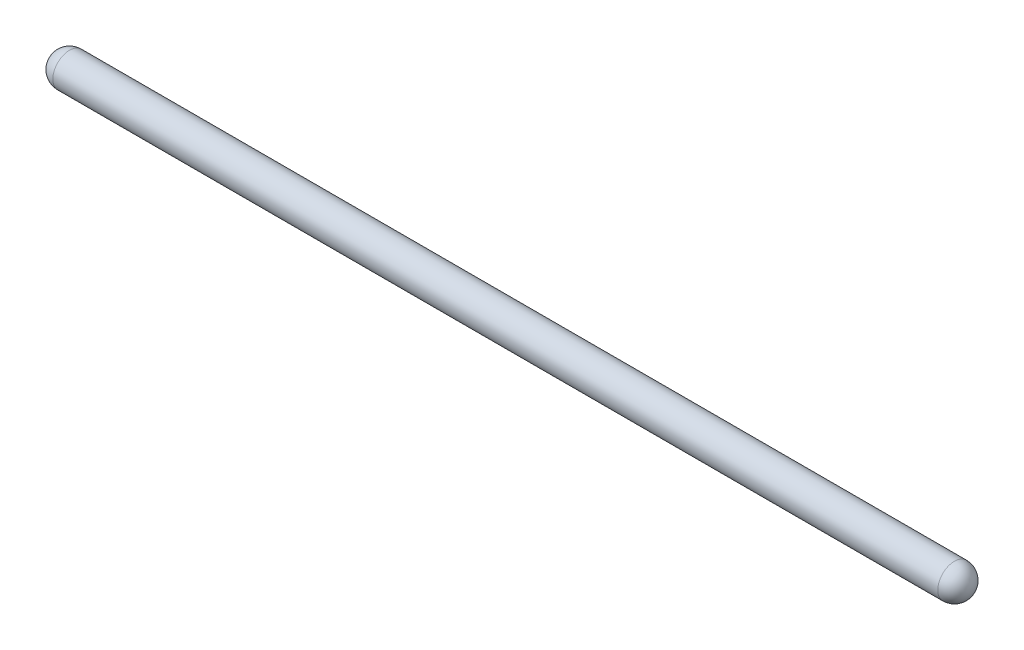
SolidWorks part; units mm, degrees
material "Brass"
ref_plane "Front Plane" through (0, 0, 0) normal (0, 0, 1) x (1, 0, 0)
ref_plane "Top Plane" through (0, 0, 0) normal (0, 1, 0) x (1, 0, 0)
ref_plane "Right Plane" through (0, 0, 0) normal (1, 0, 0) x (0, 0, -1)
sketch "Sketch1" plane through (0, 0, 0) normal (0, 0, 1) x (1, 0, 0)
  line L0 (0, 0) -> (165, 0) construction
  line L1 (3, 3) -> (162, 3)
  line L2 (165, 0) -> (0, 0)
  arc A0 (165, 0) -> (162, 3) centre (162, 0) ccw
  arc A1 (3, 3) -> (0, 0) centre (3, 0) ccw
  dimension "D3" = 3
  dimension "D1" = 3
  dimension "D2" = 162
revolve "Revolve1" add sketch "Sketch1" angle 360 about L0
ref_axis "Axis1" through (-8.25, 0, 0) along (1, 0, 0)
